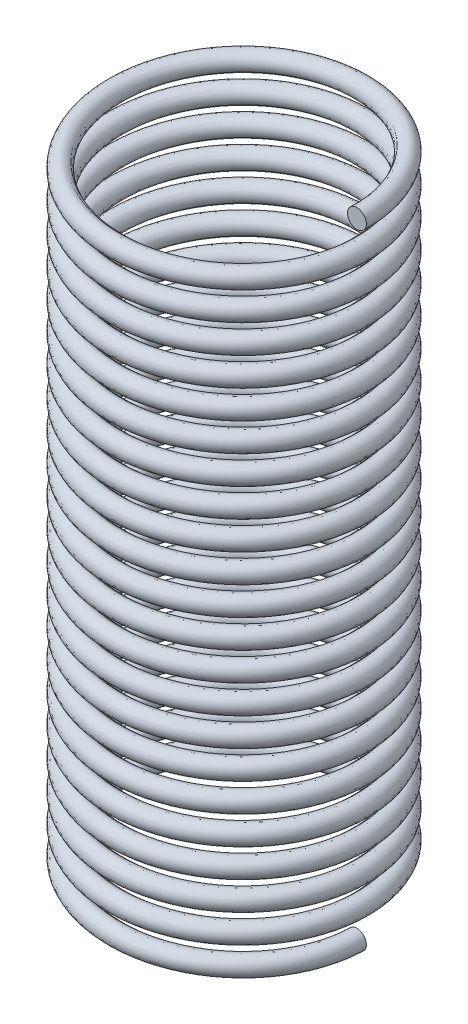
SolidWorks part; units mm, degrees
note: '?' marks a value the reader was unsure of.
ref_plane "前视基准面" through (0, 0, 0) normal (0, 0, 1) x (1, 0, 0)
ref_plane "上视基准面" through (0, 0, 0) normal (0, 1, 0) x (1, 0, 0)
ref_plane "右视基准面" through (0, 0, 0) normal (1, 0, 0) x (0, 0, -1)
sketch "草图1" plane through (0, 0, 0) normal (0, 1, 0) x (1, 0, 0)
  circle A0 centre (0, 0) radius 13
  dimension "D1" = 26
curve "螺旋线/涡状线1" pitch 3 height 66 turns 22
sketch "草图3" plane through (0, 0, 0) normal (0, 1, 0) x (1, 0, 0)
  circle A0 centre (0, 0) radius 20
ref_axis "基准轴1" through (13, 66, 0) along (0, 0, 1)?
sketch "草图4" plane through (0, 0, 0) normal (0, 0, 1) x (1, 0, 0)
  circle A0 centre (13, 66) radius 1
  point P3 (13, 66)
  dimension "D1" = 2
sweep "扫描1" add profiles "草图4" path "螺旋线/涡状线1"
